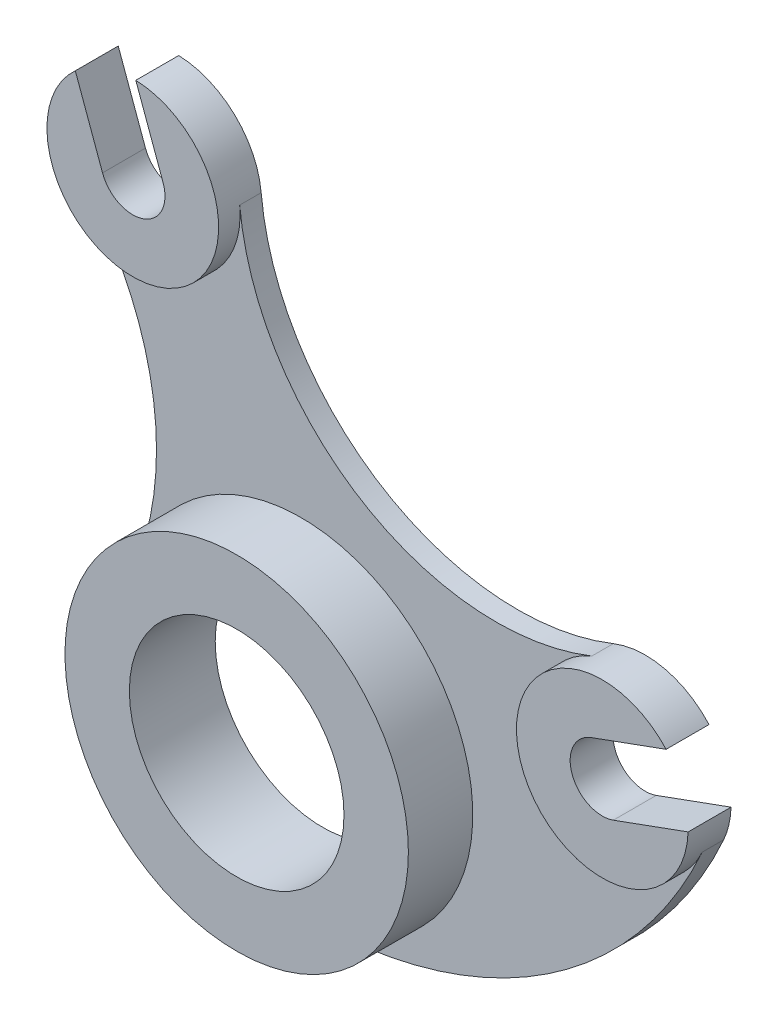
SolidWorks part; units mm, degrees
ref_plane "Front Plane" through (0, 0, 0) normal (0, 0, 1) x (1, 0, 0)
ref_plane "Top Plane" through (0, 0, 0) normal (0, 1, 0) x (1, 0, 0)
ref_plane "Right Plane" through (0, 0, 0) normal (1, 0, 0) x (0, 0, -1)
sketch "Sketch1" plane through (0, 0, 0) normal (0, 0, 1) x (1, 0, 0)
  line L0 (-56.8161, 92.385) -> (30.057, -146.2969) construction
  line L1 (-46.182, -38.895) -> (-4.0829, -23.5722) construction
  line L2 (-49.1214, -26.9559) -> (0.7199, -26.9559) construction
  line L3 (-47.8656, 95.6428) -> (-55.9189, 117.7692)
  line L4 (-65.7667, 89.1273) -> (-73.8201, 111.2537)
  line L5 (78.8354, 16.7439) -> (100.9618, 24.7972)
  line L7 (85.3509, -1.1573) -> (107.4773, 6.8961)
  circle A0 centre (-13.3796, -26.9559) radius 50.8
  circle A1 centre (-13.3796, -26.9559) radius 31.75
  arc A2 (100.9618, 24.7972) -> (107.4773, 6.8961) centre (82.0932, 7.7933) ccw
  arc A3 (78.8354, 16.7439) -> (85.3509, -1.1573) centre (82.0932, 7.7933) ccw
  arc A4 (-73.8201, 111.2537) -> (-55.9189, 117.7692) centre (-56.8161, 92.385) ccw
  arc A5 (-65.7667, 89.1273) -> (-47.8656, 95.6428) centre (-56.8161, 92.385) ccw
  arc A6 (-31.5328, 94.8161) -> (72.6492, 31.3724) centre (44.3174, 102.1095) ccw
  arc A7 (-61.2595, -9.9808) -> (-76.4235, 76.2385) centre (-145.0493, 19.7256) ccw
  arc A9 (105.2885, -2.5575) -> (-15.174, -77.7242) centre (-10.6879, 49.1965) cw
  point P7 (-13.3796, -26.9559)
  point P9 (0, 0)
  dimension "D2" = 63.5
  dimension "D3" = 101.6
  dimension "D6" = 19.05
  dimension "D7" = 19.05
  dimension "D8" = 76.2
  dimension "D9" = 127
  dimension "D10" = 88.9
  dimension "D11" = 50.8
  dimension "D12" = 50.8
  dimension "D1" = 20
  dimension "D4" = 101.6
  dimension "D5" = 127
extrude "Boss-Extrude1" add sketch "Sketch1" along normal blind 6.35 contours A9 A2 A6 A4 A7 A0 region at (3.3808, 34.8869, 0)
extrude "Boss-Extrude2" add sketch "Sketch1<3>" along normal blind 12.7 contours A5 L4 A4 L3 | A3 L5 A2 L7 region at (-51.2173, 106.9516, 0) region at (87.6765, 31.8352, 0)
sketch "Sketch1<3>" plane through (0, 0, 0) normal (0, 0, 1) x (1, 0, 0) same geometry as "Sketch1"
extrude "Boss-Extrude3" add sketch "Sketch1<4>" along normal blind 25.4 contours A0 A1 region at (-5.011, 21.6927, 0)
sketch "Sketch1<4>" plane through (0, 0, 0) normal (0, 0, 1) x (1, 0, 0) same geometry as "Sketch1"
